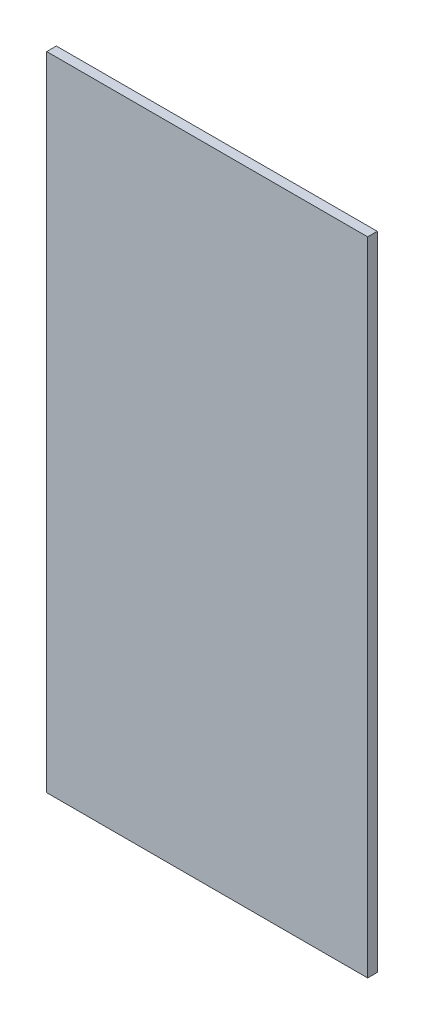
SolidWorks part; units mm, degrees
material "PET"
ref_plane "Front Plane" through (0, 0, 0) normal (0, 0, 1) x (1, 0, 0)
ref_plane "Top Plane" through (0, 0, 0) normal (0, 1, 0) x (1, 0, 0)
ref_plane "Right Plane" through (0, 0, 0) normal (1, 0, 0) x (0, 0, -1)
sketch "Sketch1" plane through (0, 0, 0) normal (0, 0, 1) x (1, 0, 0)
  line L1 (-28.5714, 377.1048) -> (171.4286, 377.1048)
  line L2 (-28.5714, 377.1048) -> (-28.5714, -22.8952)
  line L3 (-28.5714, -22.8952) -> (171.4286, -22.8952)
  line L4 (171.4286, 377.1048) -> (171.4286, -22.8952)
  dimension "D1" = 400
  dimension "D2" = 200
extrude "Boss-Extrude1" add sketch "Sketch1" along normal blind 6
